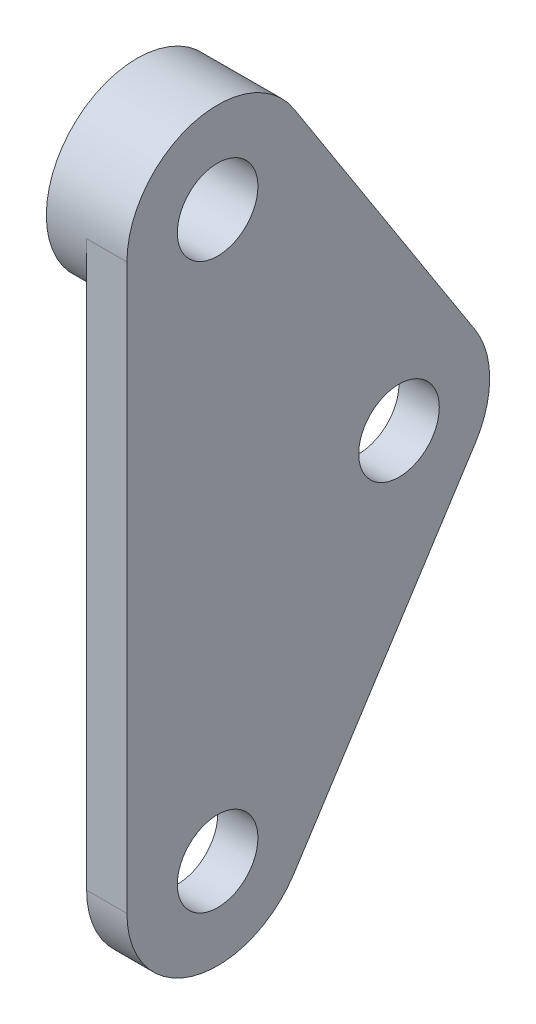
SolidWorks part; units mm, degrees
ref_plane "前视基准面" through (0, 0, 0) normal (0, 0, 1) x (1, 0, 0)
ref_plane "上视基准面" through (0, 0, 0) normal (0, 1, 0) x (1, 0, 0)
ref_plane "右视基准面" through (0, 0, 0) normal (1, 0, 0) x (0, 0, -1)
other "Configuration Table"
sketch "草图1" plane through (0, 0, 0) normal (1, 0, 0) x (0, 0, -1)
  line L0 (0, -18.5) -> (18, -18.5) construction
  line L1 (0, 0) -> (18, 0) construction
  line L2 (0, 0) -> (0, -37)
  line L3 (0, -37) -> (18, -37) construction
  line L4 (18, 0) -> (18, -37) construction
  line L5 (8.2853, -2.0666) -> (17.2853, -16.0666)
  line L6 (17.2853, -20.9334) -> (8.2853, -34.9334)
  circle A0 centre (4.5, -4.5) radius 4.5
  circle A1 centre (4.5, -32.5) radius 4.5
  circle A2 centre (13.5, -18.5) radius 4.5
  circle A3 centre (4.5, -4.5) radius 2
  circle A4 centre (13.5, -18.5) radius 2
  circle A5 centre (4.5, -32.5) radius 2
  dimension "D1" = 9
  dimension "D2" = 4
  dimension "D3" = 37
  dimension "D4" = 18
extrude "凸台-拉伸1" add sketch "草图1" along normal blind 2 contours A2 L5 A0 L2 A1 L6 | A0 | A2 | A1 region at (0, -18.5, -6.6257)
extrude "凸台-拉伸2" add sketch "草图1<4>" against normal blind 2 contours A0
sketch "草图1<4>" plane through (0, 0, 0) normal (1, 0, 0) x (0, 0, -1) same geometry as "草图1"
extrude "切除-拉伸1" cut sketch "草图1<3>" along normal through all both and the other way through all contours A3 | A4 | A5
sketch "草图1<3>" plane through (0, 0, 0) normal (1, 0, 0) x (0, 0, -1) same geometry as "草图1"
